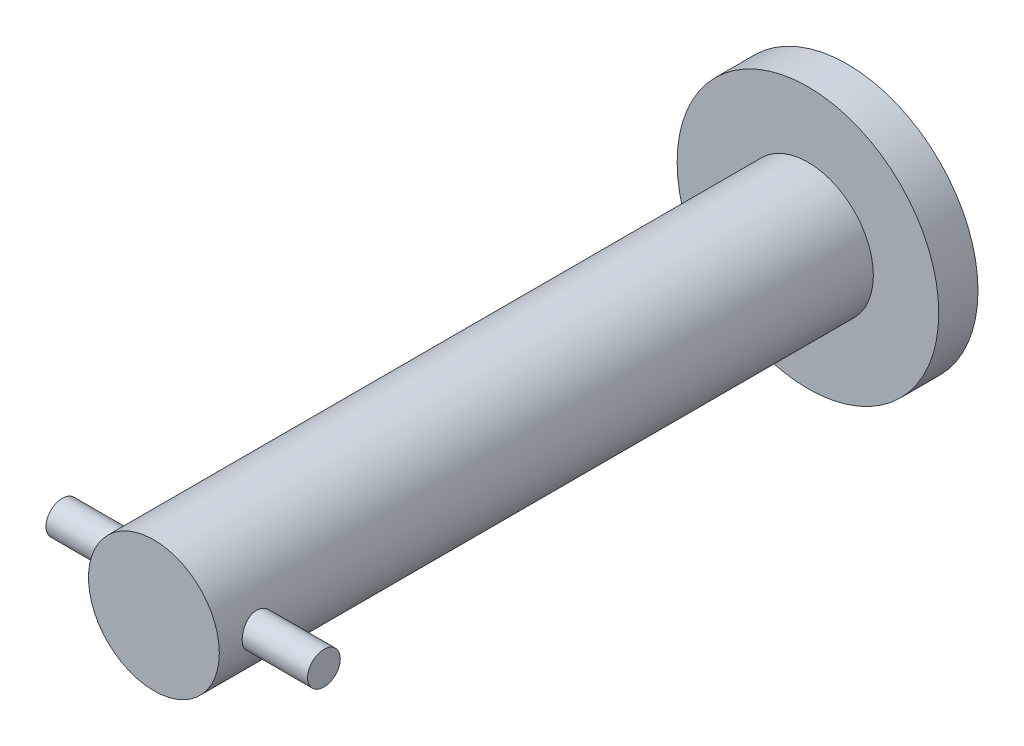
SolidWorks part; units mm, degrees
material "Cast Stainless Steel"
ref_plane "Front Plane" through (0, 0, 0) normal (0, 0, 1) x (1, 0, 0)
ref_plane "Top Plane" through (0, 0, 0) normal (0, 1, 0) x (1, 0, 0)
ref_plane "Right Plane" through (0, 0, 0) normal (1, 0, 0) x (0, 0, -1)
sketch "Sketch1" plane through (0, 0, 0) normal (0, 0, 1) x (1, 0, 0)
  circle A0 centre (0, 0) radius 5
  circle A1 centre (0, 0) radius 10
  dimension "D1" = 10
  dimension "D2" = 20
extrude "Boss-Extrude1" add sketch "Sketch1" along normal blind 5
extrude "Boss-Extrude2" add sketch "Sketch1<2>" along normal blind 55 contours A0 region at (0, 0, 0)
sketch "Sketch1<2>" plane through (0, 0, 0) normal (0, 0, 1) x (1, 0, 0) same geometry as "Sketch1"
chamfer "Chamfer1" distance 3 distance2 2 1 edges at (10, 0, 0) first distance on face at (10, 0, 0)
sketch "Sketch2" plane through (0, 0, 0) normal (1, 0, 0) x (0, 0, -1)
  line L0 (8.6955, 0) -> (-62.9768, 0) construction
  line L1 (-5, 10) -> (-5, -10) construction
  circle A0 centre (-52, 0) radius 1.25
  dimension "D1" = 2.5
  dimension "D2" = 47
extrude "Boss-Extrude3" add sketch "Sketch2" along normal blind 10 and the other way blind 10
ref_plane "Plane1" through (0, 0, 27) normal (0, 0, 1) x (1, 0, 0)
sketch "Sketch4" plane through (0, 0, 27) normal (0, 0, 1) x (1, 0, 0)
  circle A0 centre (0, 0) radius 6 construction
  dimension "D1" = 12
